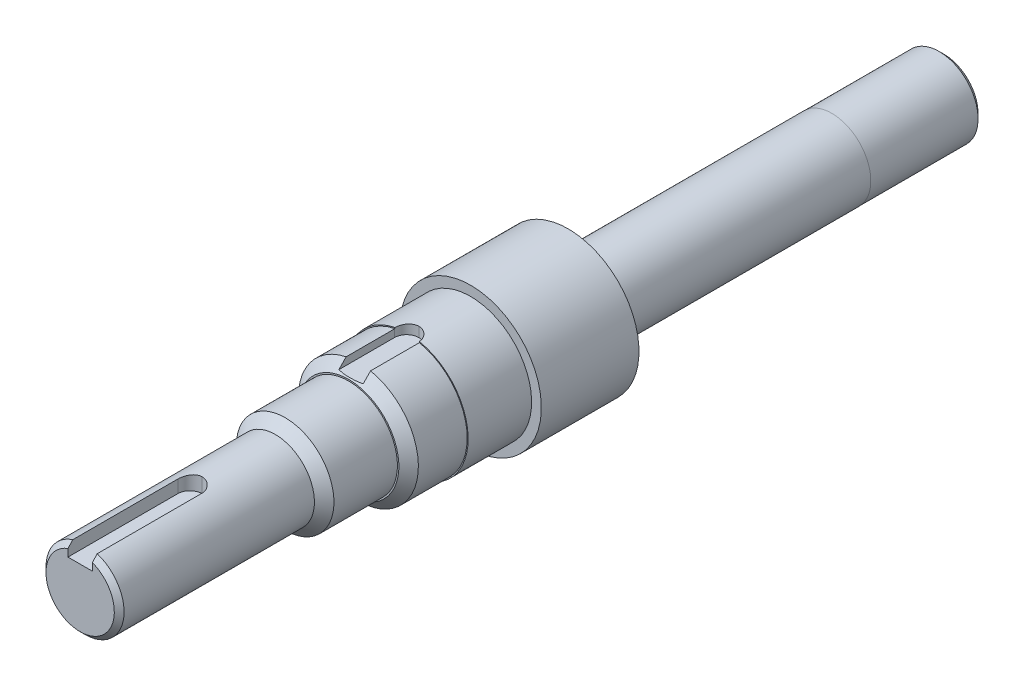
SolidWorks part; units mm, degrees
ref_plane "Front Plane" through (0, 0, 0) normal (0, 0, 1) x (1, 0, 0)
ref_plane "Top Plane" through (0, 0, 0) normal (0, 1, 0) x (1, 0, 0)
ref_plane "Right Plane" through (0, 0, 0) normal (1, 0, 0) x (0, 0, -1)
sketch "Sketch1" plane through (0, 0, 0) normal (0, 0, 1) x (1, 0, 0)
  circle A0 centre (0, 0) radius 8
  dimension "D1" = 16
extrude "Extrude1" add sketch "Sketch1" against normal blind 40
sketch "Sketch2" plane through (0, 0, 0) normal (0, 0, 1) x (1, 0, 0)
  line L1 (-2.5, 8.8722) -> (2.5, 8.8722)
  line L2 (-2.5, 8.8722) -> (-2.5, 5)
  line L3 (-2.5, 5) -> (2.5, 5)
  line L4 (2.5, 8.8722) -> (2.5, 5)
  dimension "D1" = 5
  dimension "D2" = 5
  dimension "D3" = 2.5
extrude "Cut-Extrude1" cut sketch "Sketch2" against normal blind 25
fillet "Fillet1" radius 2.5 2 edges at (2.5, 6.2997, -25) (-2.5, 6.2997, -25)
chamfer "Chamfer1" distance 1 angle 45 1 edges at (0, -8, 0)
sketch "Sketch3" plane through (0, 0, -40) normal (0, 0, -1) x (-1, 0, 0)
  circle A0 centre (0, 0) radius 10
  dimension "D1" = 20
extrude "Extrude2" add sketch "Sketch3" along normal blind 15
chamfer "Chamfer2" distance 2 angle 45 1 edges at (-10, 0, -40)
sketch "Sketch4" plane through (0, 0, -55) normal (0, 0, -1) x (-1, 0, 0)
  circle A0 centre (0, 0) radius 12.3
  dimension "D1" = 24.6
extrude "Extrude3" add sketch "Sketch4" along normal blind 12
chamfer "Chamfer3" distance 2 angle 45 1 edges at (-12.3, 0, -55)
sketch "Sketch5" plane through (0, 0, -67) normal (0, 0, -1) x (-1, 0, 0)
  circle A0 centre (0, 0) radius 12.5
  dimension "D1" = 25
extrude "Extrude4" add sketch "Sketch5" along normal blind 13
sketch "Sketch6" plane through (0, 0, -80) normal (0, 0, -1) x (-1, 0, 0)
  circle A0 centre (0, 0) radius 14.5
  dimension "D1" = 29
extrude "Extrude5" add sketch "Sketch6" along normal blind 20
sketch "Sketch9" plane through (0, 0, -100) normal (0, 0, -1) x (-1, 0, 0)
  circle A0 centre (0, 0) radius 8
  dimension "D1" = 16
ref_plane "Plane1" through (0, 0, -55) normal (0, 0, 1) x (1, 0, 0)
sketch "Sketch10" plane through (0, 0, -55) normal (0, 0, 1) x (1, 0, 0)
  line L0 (0, 15.7793) -> (0, -2.885) construction
  line L1 (-2.5, 16.6035) -> (2.5, 16.6035)
  line L2 (-2.5, 16.6035) -> (-2.5, 10.5)
  line L3 (-2.5, 10.5) -> (2.5, 10.5)
  line L4 (2.5, 16.6035) -> (2.5, 10.5)
  line L5 (19.4886, 0) -> (-1.2364, 0) construction
  dimension "D1" = 5
  dimension "D2" = 2.5
  dimension "D3" = 10.5
extrude "Cut-Extrude2" cut sketch "Sketch10" against normal blind 14.4
fillet "Fillet2" radius 2.5 2 edges at (2.5, 11.3737, -69.4) (-2.5, 11.3737, -69.4)
extrude "Extrude6" add sketch "Sketch9" along normal blind 54
ref_plane "Plane2" through (0, -5.5, 0) normal (0, 1, 0) x (-1, 0, 0)
sketch "Sketch11" plane through (0, -5.5, 0) normal (0, 1, 0) x (-1, 0, 0)
  line L0 (0, -154) -> (0, -100) construction
  line L1 (-2, -101) -> (2, -101)
  line L2 (-2, -101) -> (-2, -119)
  line L3 (-2, -119) -> (2, -119)
  line L4 (2, -101) -> (2, -119)
  line L5 (-14.5, -100) -> (14.5, -100) construction
  dimension "D1" = 4
  dimension "D2" = 18
  dimension "D3" = 2
  dimension "D4" = 1
extrude "Cut-Extrude3" cut sketch "Sketch11" against normal through all
fillet "Fillet3" radius 2 4 edges at (-2, -6.623, -119) (2, -6.623, -119) (-2, -6.623, -101) (2, -6.623, -101)
sketch "Sketch12" plane through (0, 0, -154) normal (0, 0, -1) x (-1, 0, 0)
  circle A0 centre (0, 0) radius 7.975
  dimension "D1" = 15.95
extrude "Extrude7" add sketch "Sketch12" along normal blind 23
chamfer "Chamfer4" distance 1 angle 45 1 edges at (-7.975, 0, -177)
